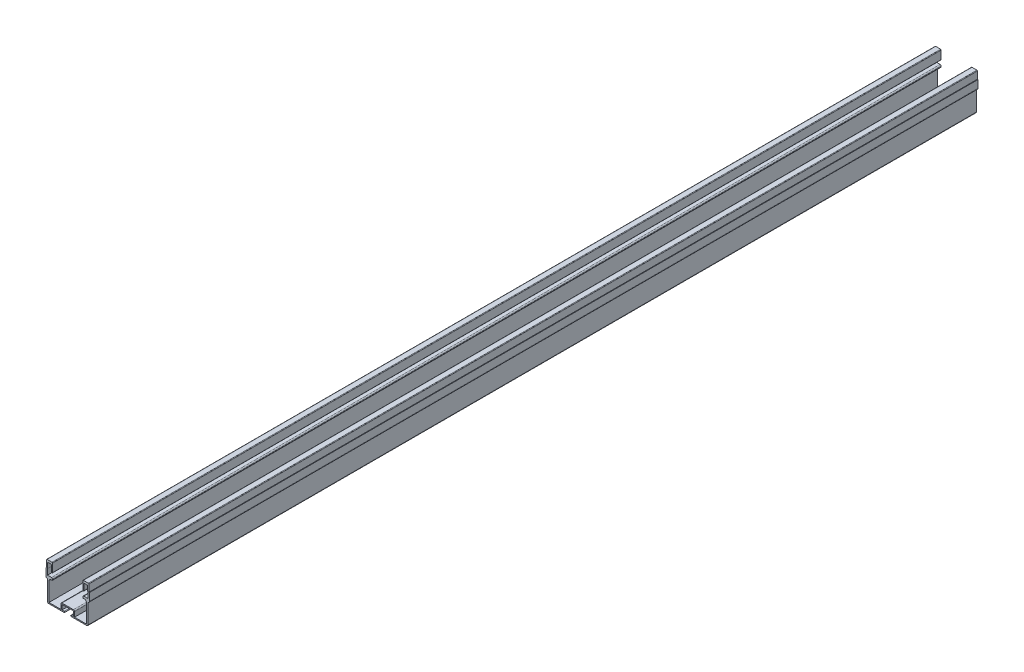
SolidWorks part; units mm, degrees
ref_plane "前视基准面" through (0, 0, 0) normal (0, 0, 1) x (1, 0, 0)
ref_plane "上视基准面" through (0, 0, 0) normal (0, 1, 0) x (1, 0, 0)
ref_plane "右视基准面" through (0, 0, 0) normal (1, 0, 0) x (0, 0, -1)
sketch "草图1" plane through (0, 0, 0) normal (0, 0, 1) x (1, 0, 0)
  line L2 (24.75, 1) -> (24.75, 5.5)
  line L3 (23.75, 6.5) -> (18.5, 6.5)
  line L4 (18.5, 6.5) -> (13.25, 6.5)
  line L5 (12.25, 5.5) -> (12.25, 1)
  line L6 (12.25, 1) -> (1.35, 1)
  line L7 (1.35, 1) -> (1.35, 18)
  line L8 (3.35, 20) -> (4.15, 20)
  line L9 (4.65, 20.5) -> (4.65, 21)
  line L10 (3.65, 22) -> (0.05, 22)
  line L11 (0.05, 22) -> (0.05, 27.3512)
  line L12 (0.05, 27.3512) -> (0.25, 27.3512)
  line L13 (0.25, 27.3512) -> (0.25, 32.3)
  line L14 (0.25, 32.3) -> (3.65, 32.3)
  line L15 (3.65, 32.3) -> (3.65, 26.3)
  line L16 (4.65, 26.3) -> (4.65, 33.8)
  line L17 (4.15, 34.3) -> (-0.35, 34.3)
  line L18 (-0.85, 33.8) -> (-0.85, 27.3512)
  line L19 (-0.85, 27.3512) -> (-1.35, 27.3512)
  line L20 (-1.35, 27.3512) -> (-1.35, 20.4509)
  line L21 (0, 19.1009) -> (0, 1)
  line L22 (1, 0) -> (15.25, 0)
  line L23 (15.25, 1) -> (13.25, 1)
  line L24 (13.25, 1) -> (13.25, 5.5)
  line L25 (13.25, 5.5) -> (18.5, 5.5)
  line L26 (18.5, 5.5) -> (23.75, 5.5)
  line L27 (23.75, 5.5) -> (23.75, 1)
  line L28 (23.75, 1) -> (21.75, 1)
  line L29 (21.75, 0) -> (36, 0)
  line L30 (37, 1) -> (37, 19.1009)
  line L31 (38.35, 20.4509) -> (38.35, 27.3512)
  line L32 (38.35, 27.3512) -> (37.85, 27.3512)
  line L33 (37.85, 27.3512) -> (37.85, 33.8)
  line L34 (37.35, 34.3) -> (32.85, 34.3)
  line L35 (32.35, 33.8) -> (32.35, 26.3)
  line L36 (33.35, 26.3) -> (33.35, 32.3)
  line L37 (33.35, 32.3) -> (36.75, 32.3)
  line L38 (36.75, 32.3) -> (36.75, 27.3512)
  line L39 (36.75, 27.3512) -> (36.95, 27.3512)
  line L40 (36.95, 27.3512) -> (36.95, 22)
  line L41 (36.95, 22) -> (33.35, 22)
  line L42 (32.35, 21) -> (32.35, 20.5)
  line L43 (32.85, 20) -> (33.65, 20)
  line L44 (35.65, 18) -> (35.65, 1)
  line L45 (35.65, 1) -> (24.75, 1)
  arc A0 (24.75, 5.5) -> (23.75, 6.5) centre (23.75, 5.5) ccw
  arc A1 (13.25, 6.5) -> (12.25, 5.5) centre (13.25, 5.5) ccw
  arc A2 (3.35, 20) -> (1.35, 18) centre (3.35, 18) ccw
  arc A3 (4.15, 20) -> (4.65, 20.5) centre (4.15, 20.5) ccw
  arc A4 (4.65, 21) -> (3.65, 22) centre (3.65, 21) ccw
  arc A5 (3.65, 26.3) -> (4.65, 26.3) centre (4.15, 26.3) ccw
  arc A6 (4.65, 33.8) -> (4.15, 34.3) centre (4.15, 33.8) ccw
  arc A7 (-0.35, 34.3) -> (-0.85, 33.8) centre (-0.35, 33.8) ccw
  arc A8 (-1.35, 20.4509) -> (0, 19.1009) centre (0, 20.4509) ccw
  arc A9 (0, 1) -> (1, 0) centre (1, 1) ccw
  arc A10 (15.25, 0) -> (15.25, 1) centre (15.25, 0.5) ccw
  arc A11 (21.75, 1) -> (21.75, 0) centre (21.75, 0.5) ccw
  arc A12 (36, 0) -> (37, 1) centre (36, 1) ccw
  arc A13 (37, 19.1009) -> (38.35, 20.4509) centre (37, 20.4509) ccw
  arc A14 (37.85, 33.8) -> (37.35, 34.3) centre (37.35, 33.8) ccw
  arc A15 (32.85, 34.3) -> (32.35, 33.8) centre (32.85, 33.8) ccw
  arc A16 (32.35, 26.3) -> (33.35, 26.3) centre (32.85, 26.3) ccw
  arc A17 (33.35, 22) -> (32.35, 21) centre (33.35, 21) ccw
  arc A18 (32.35, 20.5) -> (32.85, 20) centre (32.85, 20.5) ccw
  arc A19 (35.65, 18) -> (33.65, 20) centre (33.65, 18) ccw
extrude "凸台-拉伸1" add sketch "草图1" along normal blind 406.5 and the other way blind 406.5
